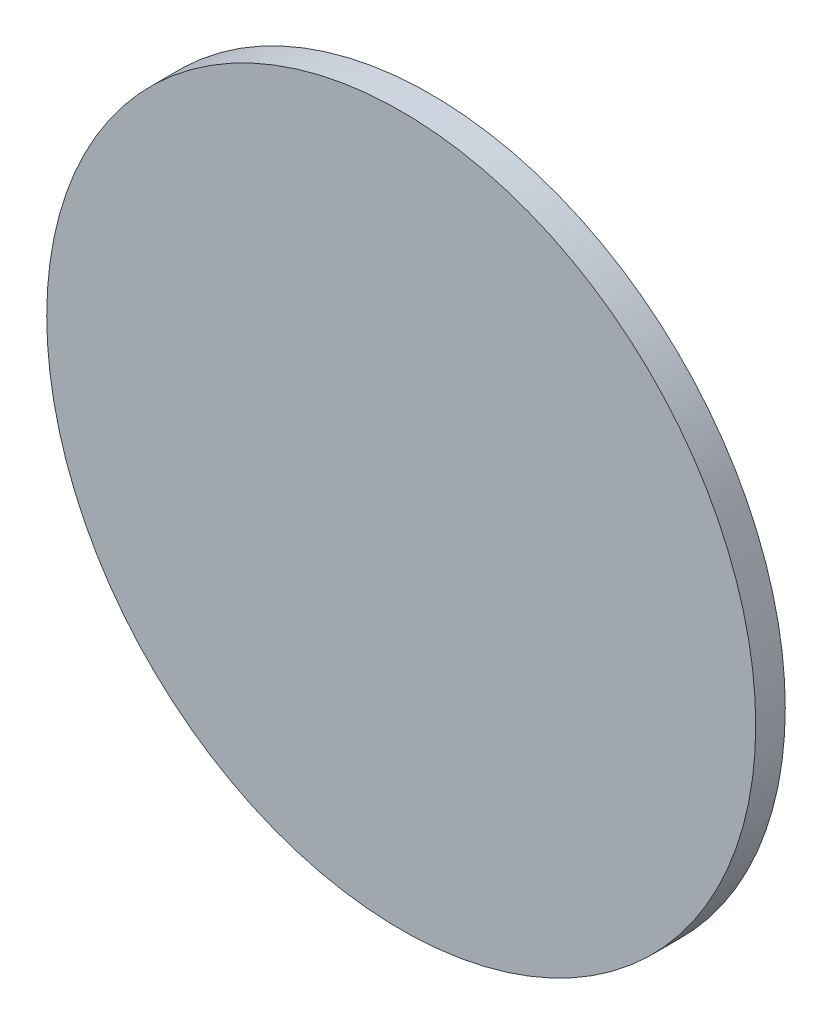
SolidWorks part; units mm, degrees
ref_plane "Front Plane" through (0, 0, 0) normal (0, 0, 1) x (1, 0, 0)
ref_plane "Top Plane" through (0, 0, 0) normal (0, 1, 0) x (1, 0, 0)
ref_plane "Right Plane" through (0, 0, 0) normal (1, 0, 0) x (0, 0, -1)
sketch "Sketch1" plane through (0, 0, 0) normal (0, 0, 1) x (1, 0, 0)
  circle A0 centre (0, 0) radius 76.2
  dimension "D1" = 152.4
extrude "Boss-Extrude1" add sketch "Sketch1" along normal blind 6.35
ref_axis "Axis1" through (0, 0, 6.35) along (0, 0, -1)
